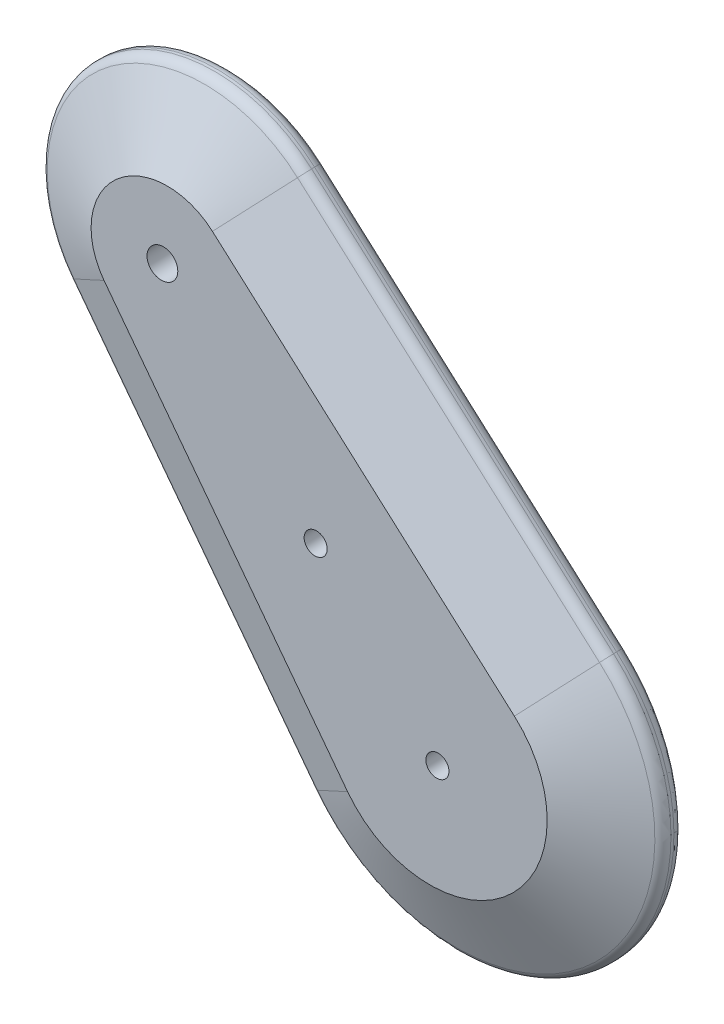
SolidWorks part; units mm, degrees
ref_plane "Front Plane" through (0, 0, 0) normal (0, 0, 1) x (1, 0, 0)
ref_plane "Top Plane" through (0, 0, 0) normal (0, 1, 0) x (1, 0, 0)
ref_plane "Right Plane" through (0, 0, 0) normal (1, 0, 0) x (0, 0, -1)
sketch "Sketch2" plane through (0.9923, 0.4478, 19.7789) normal (0.0501, 0.0226, 0.9985) x (0.9987, -0.0011, -0.0501)
  line L0 (188.2788, 112.8102) -> (195.0511, 110.2221) construction
  line L1 (195.0511, 110.2221) -> (195.3313, 110.115) construction
  line L2 (174.7001, 134.2804) -> (193.172, 118.5599)
  line L3 (168.6203, 128.9005) -> (181.9765, 108.6529)
  line L4 (188.2788, 112.8102) -> (151.6034, 154.2561) construction
  arc A0 (193.4463, 107.7251) -> (189.7396, 119.9115) centre (188.2788, 112.8102) ccw construction
  circle A2 centre (151.6034, 154.2561) radius 9.8
  circle A3 centre (151.6034, 154.2561) radius 9.8
  arc A4 (174.8886, 133.6763) -> (169.197, 128.6398) centre (172.0428, 131.1581) ccw construction
  arc A5 (181.9765, 108.6529) -> (193.172, 118.5599) centre (188.2788, 112.8102) ccw
  arc A7 (174.7001, 134.2804) -> (168.6203, 128.9005) centre (172.0428, 131.1581) ccw
  dimension "D2" = 0.3
  dimension "D3" = 0.3
  dimension "D1" = 0.3
sketch "Sketch3" plane through (0.9923, 0.4478, 19.7789) normal (0.0501, 0.0226, 0.9985) x (0.9987, -0.0011, -0.0501)
  line L1 (135.4894, 142.4096) -> (168.1363, 98.0021)
  line L2 (165.3225, 168.8089) -> (205.4277, 131.0013)
  line L3 (168.6203, 128.9005) -> (181.9765, 108.6529) construction
  line L4 (174.7001, 134.2804) -> (193.172, 118.5599) construction
  line L5 (168.6203, 128.9005) -> (181.9765, 108.6529)
  line L6 (174.7001, 134.2804) -> (193.172, 118.5599)
  arc A0 (165.3225, 168.8089) -> (135.4894, 142.4096) centre (151.6034, 154.2561) ccw
  arc A1 (168.1363, 98.0021) -> (205.4277, 131.0013) centre (188.2788, 112.8102) ccw
  arc A2 (174.7001, 134.2804) -> (168.6203, 128.9005) centre (172.0428, 131.1581) ccw construction
  arc A3 (181.9765, 108.6529) -> (193.172, 118.5599) centre (188.2788, 112.8102) ccw construction
  circle A4 centre (151.6034, 154.2561) radius 9.8 construction
  arc A5 (174.7001, 134.2804) -> (168.6203, 128.9005) centre (172.0428, 131.1581) ccw
  arc A6 (181.9765, 108.6529) -> (193.172, 118.5599) centre (188.2788, 112.8102) ccw
  circle A7 centre (151.6034, 154.2561) radius 9.8
  dimension "D1" = 40
  dimension "D2" = 50
extrude "Boss-Extrude1" add sketch "Sketch3" along normal blind 5
sketch "Sketch4" plane through (1.1925, 0.5381, 23.7686) normal (0.0501, 0.0226, 0.9985) x (0.9987, -0.0011, -0.0501)
  circle A0 centre (151.6034, 154.2561) radius 9.8 construction
  circle A1 centre (151.6034, 154.2561) radius 9.8
  circle A2 centre (151.6034, 154.2561) radius 2
  dimension "D1" = 4
extrude "Boss-Extrude2" add sketch "Sketch4" along normal up to surface (1.0042 mm away) from offset 0.5 up to face at (181.4768, 121.9704, 12.9806) offset against normal yes
sketch "Sketch5" plane through (1.2428, 0.5608, 24.7714) normal (0.0501, 0.0226, 0.9985) x (0.9987, -0.0011, -0.0501)
  line L0 (188.2788, 112.8102) -> (151.6034, 154.2561) construction
  line L2 (205.4277, 131.0013) -> (165.3225, 168.8089)
  line L3 (135.4894, 142.4096) -> (168.1363, 98.0021)
  line L4 (205.4277, 131.0013) -> (165.3225, 168.8089)
  line L5 (135.4894, 142.4096) -> (168.1363, 98.0021)
  circle A1 centre (151.6034, 154.2561) radius 2
  arc A2 (165.3225, 168.8089) -> (135.4894, 142.4096) centre (151.6034, 154.2561) ccw
  arc A3 (168.1363, 98.0021) -> (205.4277, 131.0013) centre (188.2788, 112.8102) ccw
  arc A4 (165.3225, 168.8089) -> (135.4894, 142.4096) centre (151.6034, 154.2561) ccw
  arc A5 (168.1363, 98.0021) -> (205.4277, 131.0013) centre (188.2788, 112.8102) ccw
  circle A6 centre (188.2788, 112.8102) radius 1.5
  circle A7 centre (172.0428, 131.1581) radius 1.5
  circle A8 centre (172.0428, 131.1581) radius 1.3954 construction
  circle A9 centre (151.6034, 154.2561) radius 2 construction
  dimension "D2" = 3
  dimension "D1" = 0
extrude "Boss-Extrude3" add sketch "Sketch5" along normal blind 3
chamfer "Chamfer1" distance 1 angle 45 4 edges at (152.6145, 120.4507, 9.4554) (205.5813, 94.2794, 7.3906) (139.1681, 169.4814, 9.02) (186.1347, 150.1043, 7.1024)
chamfer "Chamfer2" distance 5 angle 65 4 edges at (153.0153, 120.6315, 17.4433) (205.982, 94.4602, 15.3785) (139.5689, 169.6623, 17.008) (186.5354, 150.2851, 15.0903) first distance on face at (152.84, 120.5524, 13.9486) first distance on face at (196.786, 104.5956, 12.1051) first distance on face at (145.4142, 162.7658, 13.3655) first distance on face at (186.3601, 150.206, 11.5956)
fillet "Fillet2" radius 1.5 8 edges at (205.6314, 94.302, 8.389) (152.6646, 120.4733, 10.4539) (139.2182, 169.5041, 10.0185) (139.3184, 169.5493, 12.0155) (152.7648, 120.5185, 12.4509) (205.7315, 94.3472, 10.386) (186.1848, 150.1269, 8.1009) (186.285, 150.1721, 10.0979)
fillet "Fillet3" radius 0.5 5 edges at (170.356, 134.5629, 13.2534) (184.9479, 126.74, 12.6984) (194.2822, 107.4703, 12.6664) (162.3681, 154.5715, 11.6947) (176.3211, 119.1083, 13.304)
fillet "Fillet4" radius 1 5 edges at (170.1055, 134.4499, 8.261) (184.6974, 126.627, 7.706) (194.0318, 107.3573, 7.6739) (176.0706, 118.9953, 8.3116) (162.193, 154.4924, 8.2042)
move or copy body "Body-Move/Copy2" [suppressed] bodies to move or copy 103 parameters "D1"=0, "D2"=0, "D3"=0
move or copy body "Body-Move/Copy1" [suppressed] bodies to move or copy 103 parameters "D1"=0, "D2"=0, "D3"=0
